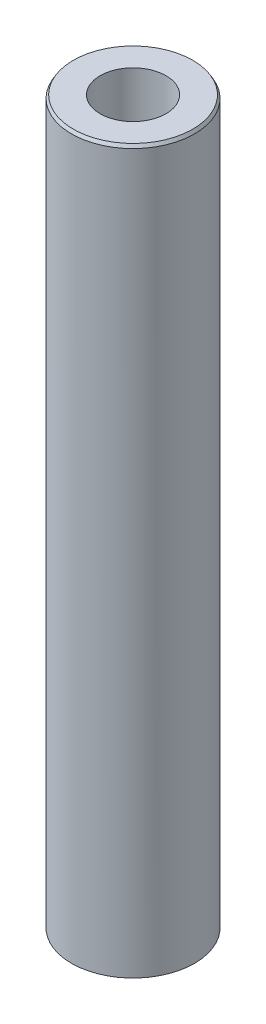
SolidWorks part; units mm, degrees
ref_plane "Front Plane" through (0, 0, 0) normal (0, 0, 1) x (1, 0, 0)
ref_plane "Top Plane" through (0, 0, 0) normal (0, 1, 0) x (1, 0, 0)
ref_plane "Right Plane" through (0, 0, 0) normal (1, 0, 0) x (0, 0, -1)
sketch "Sketch1" plane through (0, 0, 0) normal (0, 1, 0) x (1, 0, 0)
  circle A0 centre (0, 0) radius 25
  dimension "SHAFT_OD" = 50
extrude "Boss-Extrude1" add sketch "Sketch1" along normal blind 293.8029
sketch "Sketch2" plane through (0, 0, 0) normal (0, 1, 0) x (1, 0, 0)
  circle A0 centre (0, 0) radius 13.3876
  dimension "BORE_D" = 26.7752
extrude "Cut-Extrude1" cut sketch "Sketch2" along normal through all
chamfer "Chamfer1" distance 1.2852 angle 30 2 edges at (0, 293.8029, 25) (0, 0, 25) first distance on face at (0, 293.8029, 25) first distance on face at (0, 0, 13.3876)
